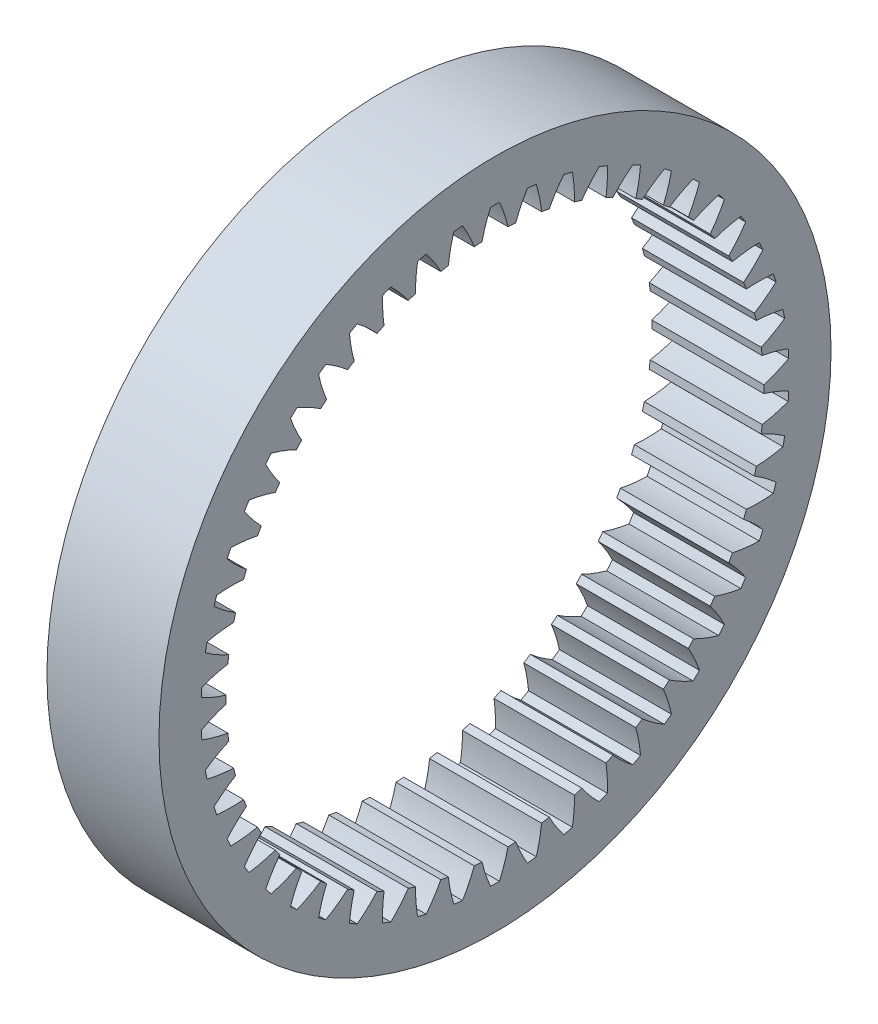
SolidWorks part; units mm, degrees
ref_plane "Plane1" through (0, 0, 0) normal (0, 0, 1) x (1, 0, 0)
ref_plane "Plane2" through (0, 0, 0) normal (0, 1, 0) x (1, 0, 0)
ref_plane "Plane3" through (0, 0, 0) normal (1, 0, 0) x (0, 0, -1)
other "Configuration Table"
sketch "HoldingSke" plane through (0, 0, 0) normal (0, 1, 0) x (1, 0, 0)
  line L0 (0, 0) -> (0.6428, -0.766)
  line L1 (-15, 0) -> (100, 0) construction
  line L2 (0, 0) -> (-2.1039, 2.3779)
  line L3 (0, 0) -> (-11.863, 4.5341)
  line L4 (0, 0) -> (5.5511, 6.6156)
  line L5 (0, 0) -> (-23.7986, -8.8762)
  line L6 (0, 0) -> (-10.5278, -7.1032)
  line L7 (-2.1039, 2.3779) -> (3.3635, 27.1825)
  line L8 (-76.2, 3.3779) -> (-54.61, 3.3779)
  line L9 (-67.7845, 28.3722) -> (-49.3413, 33.142)
  line L10 (-76.2, 71.12) -> (104.1128, 71.12)
  line L11 (0, 0) -> (-10, 0)
  line L12 (-76.2, 101.6) -> (-76.162, 101.6)
  line L13 (24.9733, 27.94) -> (52.9518, 28.4284)
  line L14 (24.9733, 27.94) -> (24.9743, 27.94)
  line L15 (24.9733, 27.94) -> (100.4006, 29.5858)
  circle A0 centre (0, 0) radius 30
  circle A1 centre (0, 0) radius 12.7
  circle A2 centre (0, 0) radius 12.7
  dimension "Num_teeth" = 50
  dimension "Pitch_radius" = 180.3128
  dimension "Width" = 10
  dimension "Diameter" = 60
sketch "BasProSke" plane through (0, 0, 0) normal (0, 1, 0) x (1, 0, 0)
  line L0 (-10, 0) -> (60, 0) construction
  line L1 (0, 24) -> (0, 30)
  line L2 (0, 24) -> (10, 24)
  line L3 (10, 24) -> (10, 30)
  line L4 (10, 30) -> (0, 30)
  dimension "Thickness" = 10
  dimension "Diameter" = 60
revolve "Base-Revolve" add sketch "BasProSke" angle 360 about L0
sketch "TooCutSke" plane through (0, 0, 0) normal (1, 0, 0) x (0, 0, -1)
  line L3 (0.8803, 24.9845) -> (0.8803, 53.6633) construction
  line L4 (0, 0) -> (0, 59.563) construction
  line L5 (0, 0) -> (-4.2903, 68.1927) construction
  line L6 (-11.0118, 21.1336) -> (36.4003, 24.1165) construction
  circle A0 centre (0, 0) radius 25 construction
  circle A1 centre (0, 0) radius 26.251 construction
  circle A2 centre (0, 0) radius 21.7833 construction
  circle A3 centre (0, 0) radius 23.9746 construction
  arc A4 (1.1677, 23.9461) -> (0.394, 26.248) centre (-11.0118, 21.1336) ccw
  arc A5 (1.1677, 23.9461) -> (-1.1677, 23.9461) centre (0, 0) ccw
  arc A6 (0.394, 26.248) -> (-0.394, 26.248) centre (0, 0) ccw
  arc A7 (-0.394, 26.248) -> (-1.1677, 23.9461) centre (11.0118, 21.1336) ccw
extrude "ToothCut" cut sketch "TooCutSke" along normal through all
fillet "Breaks" [suppressed] radius 0.1
fillet "RootFillets" [suppressed] radius 0.251
pattern_circular "TeethCuts" count 50 every 7.2 about axis through (-10, 0, 0) along (1, 0, 0) of "RootFillets", "Breaks", "ToothCut"
equation "' \"Module@HoldingSke\" = 6.35"
equation "' \"Num_teeth@HoldingSke\" = 24"
equation "' \"Ap@HoldingSke\" =  14.5"
equation "' \"Ap@HoldingSke\" = 14.5"
equation "' \"Width@HoldingSke\" = 12"
equation "' \"Diameter@HoldingSke\" = 8 * 25.4"
equation "' \"Show_teeth@HoldingSke\" = 100"
equation "' \"Backlash@HoldingSke\" = 0.009 * 25.4"
equation "' \"Addendum_fac@HoldingSke\" = 1.0"
equation "' \"Dedendum_fac@HoldingSke\" = 1.25"
equation "' \"Dedendum_add@HoldingSke\" = 0.00005 * 25.4"
equation "' \"Clearance_fac@HoldingSke\" = 0.25"
equation "\"Pitch@HoldingSke\" = 1 / \"Module@HoldingSke\" "
equation "\"Overcut_dia@TooCutSke\" = (\"Num_teeth@HoldingSke\" - 2 * \"Addendum_fac@HoldingSke\") / \"Pitch@HoldingSke\" - 0.002 * 25.4"
equation "\"Pitch_dia@TooCutSke\" = \"Num_teeth@HoldingSke\" / \"Pitch@HoldingSke\""
equation "\"Base_dia@TooCutSke\" = \"Num_teeth@HoldingSke\" / \"Pitch@HoldingSke\" * cos((\"Ap@HoldingSke\"  * 3.14159265 / 180)) * 0.90"
equation "\"Root_dia@TooCutSke\" = \"Num_teeth@HoldingSke\"  / \"Pitch@HoldingSke\" + 2 *  \"Dedendum_fac@HoldingSke\"/ \"Pitch@HoldingSke\" + \"Dedendum_add@HoldingSke\" * 2"
equation "\"Half_ang@TooCutSke\" = 180 / \"Num_teeth@HoldingSke\""
equation "\"Half_CT@TooCutSke\" = \"Num_teeth@HoldingSke\" / \"Pitch@HoldingSke\" * sin((3.14159265 / 2 / \"Num_teeth@HoldingSke\")) / 2 + 10 * \"Backlash@HoldingSke\" / 4"
equation "\"Flank_rad@TooCutSke\" = \"Num_teeth@HoldingSke\" / \"Pitch@HoldingSke\" / 4"
equation "\"Radius@RootFillets\"= \"Clearance_fac@HoldingSke\" / \"Pitch@HoldingSke\" + \"Dedendum_add@HoldingSke\""
equation "\"Break_rad@Breaks\" = 0.02 / \"Pitch@HoldingSke\" * 5"
equation "\"Num_teeth@TeethCuts\" = int( \"Show_teeth@HoldingSke\" ) + 1"
equation "\"Num_teeth@TeethCuts\" = ((sgn( \"Num_teeth@TeethCuts\" - \"Num_teeth@HoldingSke\" )-1)*( \"Num_teeth@TeethCuts\" - \"Num_teeth@HoldingSke\" ))/-2+ \"Num_teeth@HoldingSke\""
equation "\"Num_teeth@TeethCuts\" = ((sgn( \"Num_teeth@TeethCuts\" - 2.0)+1)*( \"Num_teeth@TeethCuts\" - 2.0))/2 +2.0"
equation "\"Angle@TeethCuts\" = 360.0 / \"Num_teeth@HoldingSke\""
equation "\"Diameter@BasProSke\" = \"Num_teeth@HoldingSke\"  / \"Pitch@HoldingSke\" + 2 *  \"Dedendum_fac@HoldingSke\"/ \"Pitch@HoldingSke\" + \"Dedendum_add@HoldingSke\" * 2 + 0.002 * 25.4"
equation "\"Diameter@BasProSke\" = ((sgn( \"Diameter@BasProSke\"  - \"Diameter@HoldingSke\" )+1)*( \"Diameter@BasProSke\"  - \"Diameter@HoldingSke\" ))/2 + \"Diameter@HoldingSke\""
equation "\"Inside_diameter@BasProSke\" =  (\"Num_teeth@HoldingSke\" - 2 * \"Addendum_fac@HoldingSke\") / \"Pitch@HoldingSke\" "
equation "\"Thickness@BasProSke\"  = \"Width@HoldingSke\""
